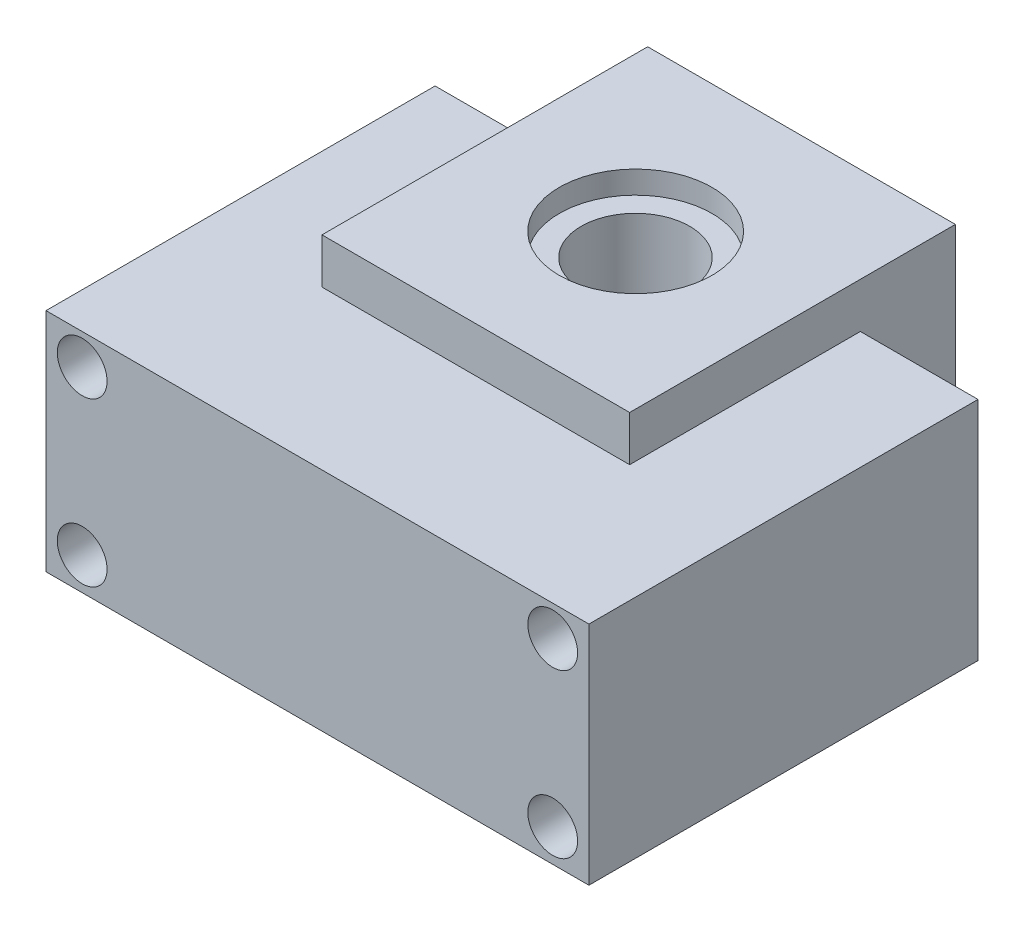
SolidWorks part; units mm, degrees
material "Chrome Stainless Steel"
ref_plane "Front Plane" through (0, 0, 0) normal (0, 0, 1) x (1, 0, 0)
ref_plane "Top Plane" through (0, 0, 0) normal (0, 1, 0) x (1, 0, 0)
ref_plane "Right Plane" through (0, 0, 0) normal (1, 0, 0) x (0, 0, -1)
sketch "Sketch1" plane through (0, 0, 0) normal (0, 1, 0) x (1, 0, 0)
  line L1 (0, 0) -> (60, 0)
  line L2 (0, 0) -> (0, 43)
  line L3 (0, 43) -> (60, 43)
  line L4 (60, 0) -> (60, 43)
  dimension "D1" = 60
  dimension "D2" = 43
extrude "Boss-Extrude1" add sketch "Sketch1" along normal blind 25
sketch "Sketch2" plane through (0, 25, 0) normal (0, 1, 0) x (1, 0, 0)
  line L0 (30, 0) -> (30, 43) construction
  line L1 (0, 0) -> (60, 0) construction
  line L2 (60, 43) -> (0, 43) construction
  line L3 (0, 8.5) -> (60, 8.5) construction
  line L4 (0, 43) -> (0, 0) construction
  line L5 (60, 0) -> (60, 43) construction
  line L7 (13, 43) -> (47, 43)
  line L8 (13, 43) -> (13, 17.5)
  line L9 (13, 17.5) -> (47, 17.5)
  line L10 (47, 43) -> (47, 17.5)
  dimension "D1" = 8.5
  dimension "D2" = 34
  dimension "D3" = 17
  dimension "D4" = 25.5
extrude "Boss-Extrude2" add sketch "Sketch2" along normal blind 5
sketch "Sketch5" plane through (0, 0, -43) normal (0, 0, -1) x (-1, 0, 0)
  line L1 (-47, 30) -> (-12.9927, 30)
  line L2 (-47, 30) -> (-47, 0)
  line L3 (-47, 0) -> (-12.9927, 0)
  line L4 (-12.9927, 30) -> (-12.9927, 0)
  dimension "D1" = 30
extrude "Boss-Extrude3" add sketch "Sketch5" along normal blind 10.5
sketch "Sketch6" plane through (0, 30, 0) normal (0, 1, 0) x (1, 0, 0)
  line L0 (29.9964, 53.5) -> (30, 17.5) construction
  line L1 (12.9927, 53.5) -> (47, 53.5) construction
  line L2 (13, 17.5) -> (47, 17.5) construction
  line L3 (47, 35.5) -> (13, 35.5) construction
  line L4 (47, 17.5) -> (47, 53.5) construction
  line L5 (13, 43) -> (13, 17.5) construction
  circle A0 centre (29.9982, 35.1447) radius 6
  dimension "D1" = 12
extrude "Cut-Extrude1" cut sketch "Sketch6" against normal through all
sketch "Sketch7" plane through (0, 30, 0) normal (0, 1, 0) x (1, 0, 0)
  line L0 (29.9964, 53.5) -> (30, 17.5) construction
  line L1 (12.9927, 53.5) -> (47, 53.5) construction
  line L2 (13, 17.5) -> (47, 17.5) construction
  circle A0 centre (29.9982, 35.1659) radius 5.9788
  circle A1 centre (29.9982, 35.1659) radius 8.4376
extrude "Cut-Extrude2" cut sketch "Sketch7" against normal mid plane 5 contours A1 | A0
sketch "Sketch8" plane through (0, 0, 0) normal (0, 0, 1) x (1, 0, 0)
  line L0 (0, 25) -> (0, 0) construction
  line L1 (60, 25) -> (60, 0) construction
  circle A0 centre (4, 21.6054) radius 2.75
  circle A1 centre (56, 21.6054) radius 2.75
  circle A2 centre (56, 3.6054) radius 2.75
  circle A3 centre (4, 3.6054) radius 2.75
  dimension "D1" = 5.5
  dimension "D4" = 4
  dimension "D5" = 4
  dimension "D2" = 2
  dimension "D3" = 2
extrude "Cut-Extrude3" cut sketch "Sketch8" against normal blind 10
equation "\"4mmm\"=1"
